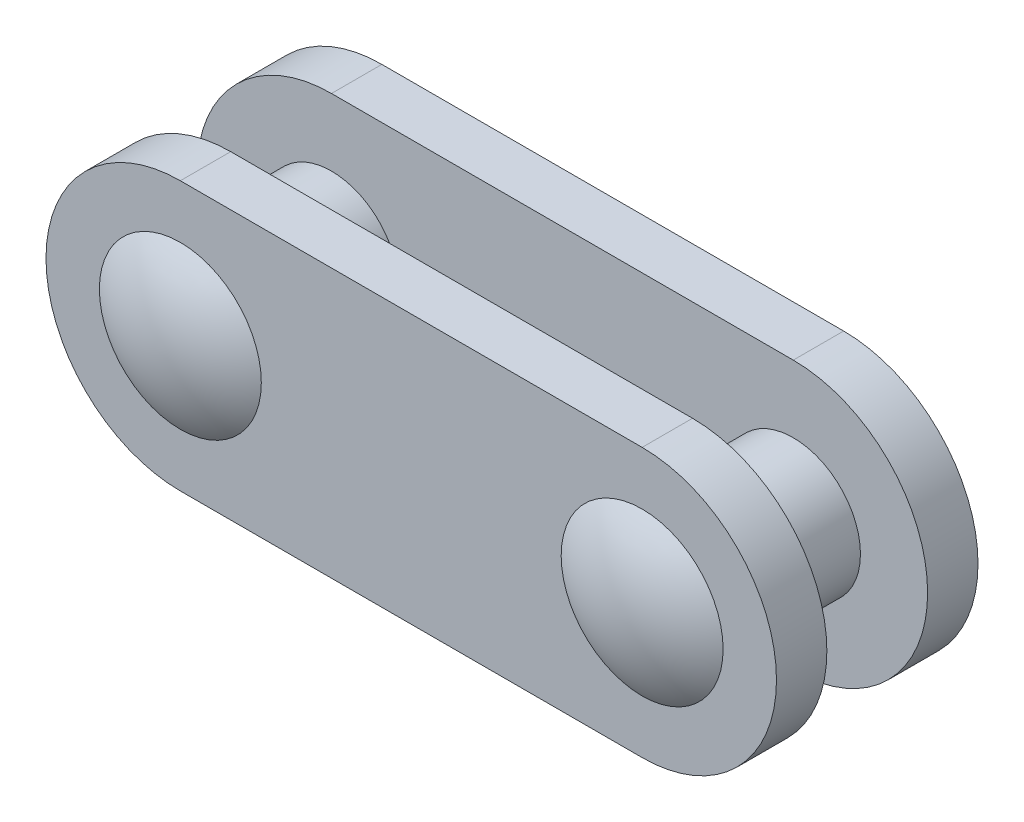
SolidWorks part; units mm, degrees
ref_plane "前视基准面" through (0, 0, 0) normal (0, 0, 1) x (1, 0, 0)
ref_plane "上视基准面" through (0, 0, 0) normal (0, 1, 0) x (1, 0, 0)
ref_plane "右视基准面" through (0, 0, 0) normal (1, 0, 0) x (0, 0, -1)
ref_plane "基准面1" through (0, 0, 0) normal (0, 0, 1) x (1, 0, 0)
sketch "草图1" plane through (0, 0, 0) normal (0, 0, 1) x (1, 0, 0)
  line L0 (0, -8) -> (27.5, -8)
  line L1 (27.5, 8) -> (0, 8)
  arc A0 (0, 8) -> (0, -8) centre (0, 0) ccw
  arc A1 (27.5, -8) -> (27.5, 8) centre (27.5, 0) ccw
extrude "凸台-拉伸1" add sketch "草图1" against normal blind 6 and the other way blind 6
ref_plane "基准面2" through (0, 0, 0) normal (1, 0, 0) x (0, 0, -1)
sketch "草图2" plane through (0, 0, 0) normal (1, 0, 0) x (0, 0, -1)
  line L0 (-6, 4.8218) -> (-6, 4)
  line L1 (-6, 4) -> (6, 4)
  line L2 (6, 4) -> (6, 4.5)
  line L3 (6, 4.5) -> (7, 4.5)
  line L4 (7, 4.5) -> (7, 0)
  line L5 (7, 0) -> (-7.5, 0)
  line L6 (7, 0) -> (-7.5, 0) construction
  arc A0 (-7.5, 0) -> (-6, 4.8218) centre (1, 0) cw
revolve "旋转1" add sketch "草图2" angle 360 about L6 reverse direction yes
ref_plane "基准面3" through (0, 0, 7.5) normal (0, 0, 1) x (1, 0, 0)
ref_plane "基准面4" through (27.5, 0, 0) normal (1, 0, 0) x (0, 0, -1)
sketch "草图3" plane through (27.5, 0, 0) normal (1, 0, 0) x (0, 0, -1)
  line L0 (-6, 4.8218) -> (-6, 4)
  line L1 (-6, 4) -> (6, 4)
  line L2 (6, 4) -> (6, 4.5)
  line L3 (6, 4.5) -> (7, 4.5)
  line L4 (7, 4.5) -> (7, 0)
  line L5 (7, 0) -> (-7.5, 0)
  line L6 (7, 0) -> (-7.5, 0) construction
  arc A0 (-7.5, 0) -> (-6, 4.8218) centre (1, 0) cw
revolve "旋转2" add sketch "草图3" angle 360 about L6 reverse direction yes
ref_plane "基准面5" through (0, 0, 0) normal (0, 0, 1) x (1, 0, 0)
sketch "草图4" plane through (0, 0, 0) normal (0, 0, 1) x (1, 0, 0)
  line L0 (0, -8) -> (27.5, -8)
  line L1 (27.5, 8) -> (0, 8)
  arc A0 (0, 8) -> (0, -8) centre (0, 0) ccw
  arc A1 (27.5, -8) -> (27.5, 8) centre (27.5, 0) ccw
  circle A2 centre (27.5, 0) radius 4
  circle A3 centre (0, 0) radius 4
extrude "切除-拉伸1" cut sketch "草图4" along normal blind 3 and the other way blind 3
ref_plane "基准面6" through (0, 0, 0) normal (0, 0, 1) x (1, 0, 0)
ref_plane "cp2 XY" through (0, 0, 0) normal (0, 0, -1) x (-1, 0, 0)
ref_plane "cp2 XZ" through (0, 0, 0) normal (0, 1, 0) x (1, 0, 0)
ref_plane "cp2 YZ" through (0, 0, 0) normal (1, 0, 0) x (0, 0, -1)
ref_axis "cp2 X" through (-80.9, 0, 0) along (1, 0, 0)
ref_axis "cp2 Y" through (0, 50, 0) along (0, -1, 0)
ref_axis "cp2 Z" through (0, 0, -80.9) along (0, 0, 1)
sketch3d "cp2"
  point P0 (0, 0, 0)
ref_plane "cp4 XY" through (0, 0, 0) normal (0, 0, -1) x (-1, 0, 0)
ref_plane "cp4 XZ" through (0, 0, 0) normal (0, 1, 0) x (1, 0, 0)
ref_plane "cp4 YZ" through (27.5, 0, 0) normal (1, 0, 0) x (0, 0, -1)
ref_axis "cp4 X" through (-80.9, 0, 0) along (1, 0, 0)
ref_axis "cp4 Y" through (27.5, 50, 0) along (0, -1, 0)
ref_axis "cp4 Z" through (27.5, 0, -80.9) along (0, 0, 1)
sketch3d "cp4"
  point P0 (27.5, 0, 0)
equation "\"零件重量\"= \"SW-质量\""
